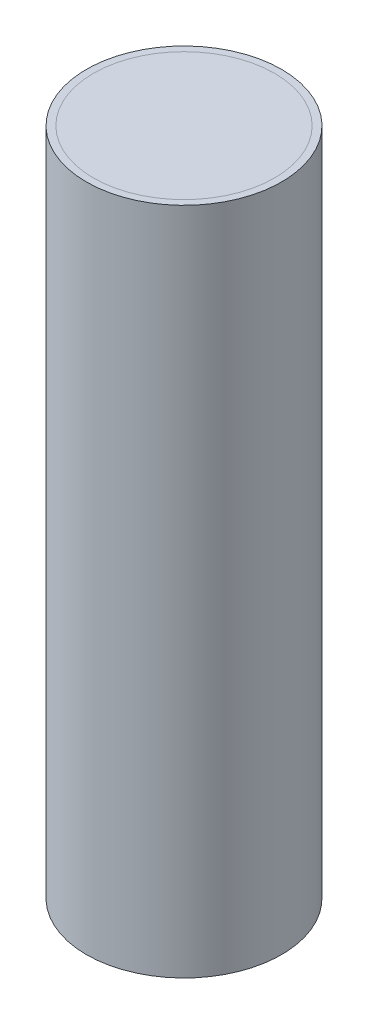
SolidWorks part; units mm, degrees
ref_plane "Front Plane" through (0, 0, 0) normal (0, 0, 1) x (1, 0, 0)
ref_plane "Top Plane" through (0, 0, 0) normal (0, 1, 0) x (1, 0, 0)
ref_plane "Right Plane" through (0, 0, 0) normal (1, 0, 0) x (0, 0, -1)
sketch "Sketch1" plane through (0, 0, 0) normal (0, 1, 0) x (1, 0, 0)
  circle A0 centre (0, 0) radius 44.45
  circle A1 centre (0, 0) radius 41.275
  dimension "D1" = 88.9
  dimension "D2" = 82.55
extrude "Boss-Extrude1" add sketch "Sketch1" along normal blind 304.8
extrude "Boss-Extrude2" add sketch "Sketch1<2>" along normal blind 304.8 separate body contours A1 region at (0, 0, 0)
sketch "Sketch1<2>" plane through (0, 0, 0) normal (0, 1, 0) x (1, 0, 0) same geometry as "Sketch1"
ref_plane "Plane1" through (0, 152.4, 0) normal (0, 1, 0) x (-1, 0, 0)
